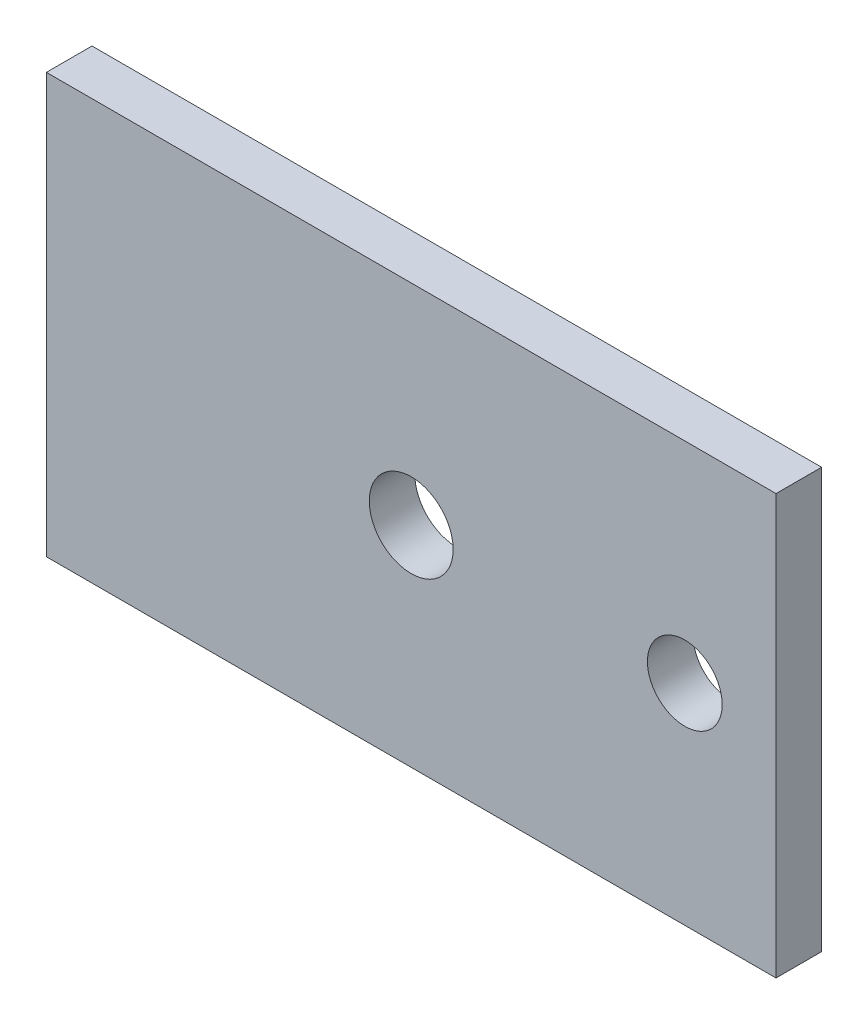
SolidWorks part; units mm, degrees
ref_plane "Front Plane" through (0, 0, 0) normal (0, 0, 1) x (1, 0, 0)
ref_plane "Top Plane" through (0, 0, 0) normal (0, 1, 0) x (1, 0, 0)
ref_plane "Right Plane" through (0, 0, 0) normal (1, 0, 0) x (0, 0, -1)
sketch "Sketch1" plane through (0, 0, 0) normal (0, 0, 1) x (1, 0, 0)
  line L0 (-25.3491, 0) -> (24.7222, 0) construction
  line L1 (40, -23) -> (-40, -23)
  line L2 (40, -23) -> (40, 23)
  line L3 (40, 23) -> (-40, 23)
  line L4 (-40, -23) -> (-40, 23)
  line L5 (40, -23) -> (-40, 23) construction
  line L6 (40, 23) -> (-40, -23) construction
  circle A0 centre (0, 0) radius 4.6
  circle A1 centre (30, 0) radius 4.1
  point P0 (0, 0)
  dimension "D1" = 9.2
  dimension "D2" = 8.2
  dimension "D3" = 46
  dimension "D4" = 30
  dimension "D5" = 80
extrude "Boss-Extrude1" add sketch "Sketch1" along normal blind 5
